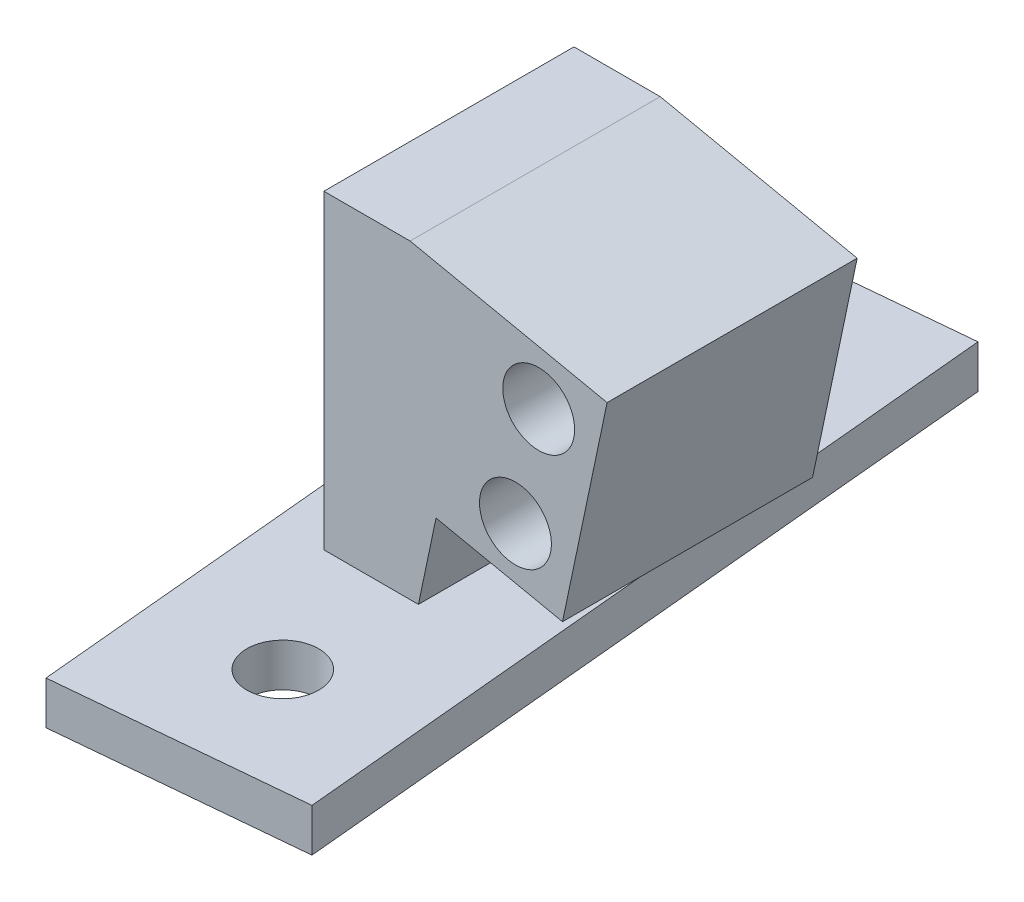
SolidWorks part; units mm, degrees
ref_plane "Front Plane" through (0, 0, 0) normal (0, 0, 1) x (1, 0, 0)
ref_plane "Top Plane" through (0, 0, 0) normal (0, 1, 0) x (1, 0, 0)
ref_plane "Right Plane" through (0, 0, 0) normal (1, 0, 0) x (0, 0, -1)
sketch "Sketch1" plane through (0, 0, 0) normal (0, 0, 1) x (1, 0, 0)
  line L0 (-629.0113, 228.5148) -> (-646.4173, 232.1744)
  line L1 (-625.5069, 227.7779) -> (-640.2031, 230.8679) construction
  line L2 (-646.4173, 232.1744) -> (-650.3578, 213.4325)
  line L3 (-650.3578, 213.4325) -> (-632.9518, 209.7729)
  line L4 (-626.0822, 208.3286) -> (-644.038, 212.1038) construction
  line L5 (-632.9518, 209.7729) -> (-629.0113, 228.5148)
  circle A0 centre (-635.0536, 225) radius 3.175
  circle A1 centre (-637.1112, 215.214) radius 3.175
  dimension "D4" = 6.35
  dimension "D5" = 6.35
  dimension "D1" = 6.35
  dimension "D2" = 19.1516
  dimension "D3" = 17.7865
extrude "Boss-Extrude1" add sketch "Sketch1" along normal up to surface (22.098 mm away)
sketch "Sketch2" plane through (15.4424, 73.4471, 0) normal (-0.2058, -0.9786, 0) x (0.9786, -0.2058, 0)
  line L0 (-680.3571, 22.098) -> (-680.3571, 0)
  line L1 (-680.3571, 0) -> (-673.9925, 0)
  line L2 (-680.3571, 0) -> (-662.5706, 0) construction
  line L3 (-673.9925, 0) -> (-673.9925, 22.098)
  line L4 (-662.5706, 22.098) -> (-680.3571, 22.098) construction
  line L5 (-673.9925, 22.098) -> (-680.3571, 22.098)
  dimension "D1" = 6.3646
extrude "Boss-Extrude2" add sketch "Sketch2" along normal blind 8.89 contours L5 L0 L1 L3
ref_plane "Plane5" through (0, 204.7328, 0) normal (0, 1, 0) x (1, 0, 0)
sketch "Sketch12" plane through (0, 204.7328, 0) normal (0, 1, 0) x (1, 0, 0)
  line L0 (-662.5531, 20.7178) -> (-656.5069, -44.1839)
  line L1 (-656.5069, -44.1839) -> (-635.01, -42.1813)
  line L2 (-635.01, -42.1813) -> (-641.0561, 22.7204)
  line L3 (-641.0561, 22.7204) -> (-662.5531, 20.7178)
  circle A0 centre (-650.8622, 11.6029) radius 3.175
  circle A1 centre (-646.7009, -33.0664) radius 3.175
  dimension "D5" = 10.16
  dimension "D7" = 6.35
  dimension "D10" = 6.35
  dimension "D1" = 6.35
  dimension "D2" = 21.59
  dimension "D3" = 21.59
  dimension "D4" = 21.59
  dimension "D6" = 10.795
  dimension "D8" = 10.795
  dimension "D9" = 10.16
  dimension "D11" = 65.1827
extrude "Boss-Extrude6" add sketch "Sketch12" against normal blind 3.81
sketch "Sketch19" plane through (0, 0, 22.098) normal (0, 0, 1) x (1, 0, 0)
  line L0 (-646.4173, 232.1744) -> (-654.0373, 232.1744)
  line L1 (-654.0373, 232.1744) -> (-654.0373, 204.7328)
  line L2 (-662.5531, 204.7328) -> (-656.5069, 204.7328) construction
  line L3 (-654.0373, 204.7328) -> (-652.1869, 204.7328)
  line L4 (-652.1869, 204.7328) -> (-646.4173, 232.1744)
  dimension "D1" = 7.62
extrude "Boss-Extrude12" add sketch "Sketch19" against normal up to surface (22.098 mm away) up to face at (-641.73, 215.3418, 0)
